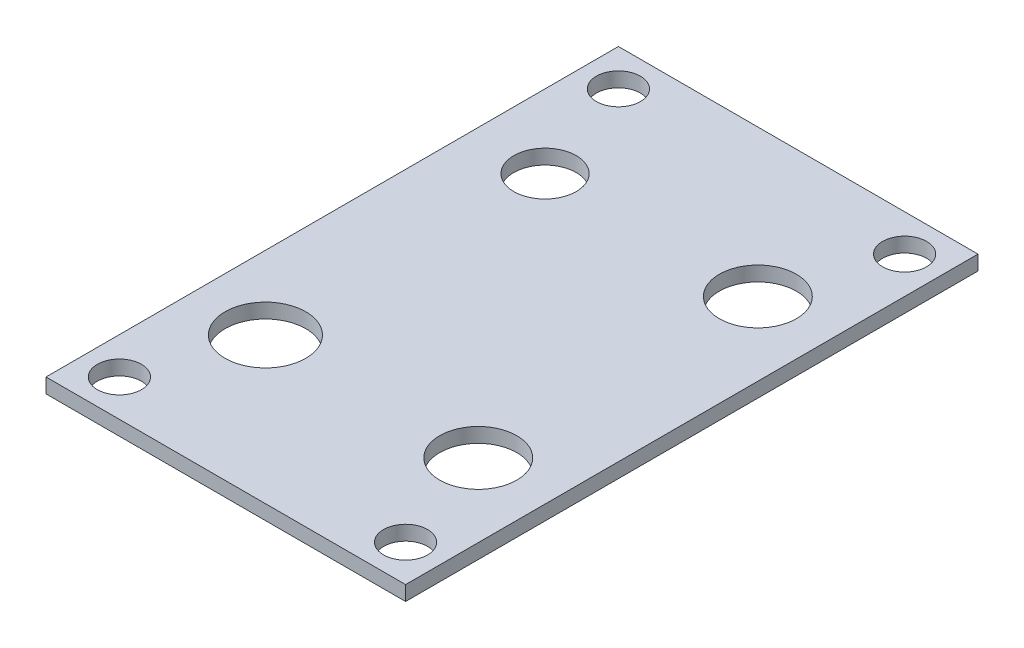
SolidWorks part; units mm, degrees
ref_plane "Alzado" through (0, 0, 0) normal (0, 0, 1) x (1, 0, 0)
ref_plane "Planta" through (0, 0, 0) normal (0, 1, 0) x (1, 0, 0)
ref_plane "Vista lateral" through (0, 0, 0) normal (1, 0, 0) x (0, 0, -1)
sketch "Croquis1" plane through (0, 0, 0) normal (0, 1, 0) x (1, 0, 0)
  line L0 (0, 37) -> (0, 32) construction
  line L1 (-24.5, 37) -> (24.5, 37)
  line L2 (-24.5, 37) -> (-24.5, -36)
  line L3 (-24.5, -36) -> (24.5, -36)
  line L4 (24.5, 37) -> (24.5, -36)
  line L5 (0, -29) -> (0, -36) construction
  line L6 (-6.25, -6.1) -> (-24.5, -6.1) construction
  line L7 (-14.5, -21.1) -> (14.5, -21.1) construction
  circle A0 centre (14.5, -21.1) radius 5.25
  circle A1 centre (-14.5, -21.1) radius 5.5
  circle A2 centre (-14.5, 17) radius 4.25
  circle A3 centre (14.5, 17) radius 5.25
  circle A6 centre (-19.5, 32) radius 3
  circle A7 centre (19.5, 32) radius 3
  point P0 (0, 0)
  point P10 (0, -17.55)
  dimension "D8" = 14.9
  dimension "D16" = 10.5
  dimension "D17" = 11
  dimension "D18" = 10
  dimension "D10" = 20
  dimension "D11" = 20
  dimension "D13" = 10
  dimension "D14" = 8.5
  dimension "D15" = 10.5
  dimension "D9" = 10
  dimension "D19" = 10
  dimension "D30" = 5
  dimension "D31" = 6
  dimension "D32" = 5
  dimension "D33" = 5
  dimension "D34" = 5
  dimension "D35" = 6
  dimension "D4" = 5
  dimension "D6" = 7
  dimension "D12" = 49
  dimension "D20" = 73
  dimension "D22" = 15
extrude "Saliente-Extruir4" add sketch "Croquis1" along normal blind 2
sketch "Croquis7" plane through (0, 2, 0) normal (0, 1, 0) x (1, 0, 0)
  line L1 (-24.5, -36) -> (24.5, -36)
  line L2 (-24.5, -36) -> (-24.5, -41)
  line L3 (-24.5, -41) -> (24.5, -41)
  line L4 (24.5, -36) -> (24.5, -41)
  dimension "D1" = 49
  dimension "D2" = 5
extrude "Saliente-Extruir5" add sketch "Croquis7" against normal up to surface (2 mm away) up to face at (0, 0, -0.5)
sketch "Croquis8" plane through (0, 2, 0) normal (0, 1, 0) x (1, 0, 0)
  line L0 (-19.5, -36) -> (19.5, -36) construction
  line L1 (-24.5, -41) -> (24.5, -41) construction
  line L2 (24.5, -41) -> (24.5, 37) construction
  line L3 (-24.5, 37) -> (-24.5, -41) construction
  circle A0 centre (-19.5, -36) radius 3
  circle A1 centre (19.5, -36) radius 3
  dimension "D2" = 5
  dimension "D3" = 6
  dimension "D4" = 5
  dimension "D5" = 6
  dimension "D1" = 5
extrude "Cortar-Extruir2" cut sketch "Croquis8" against normal blind 10
